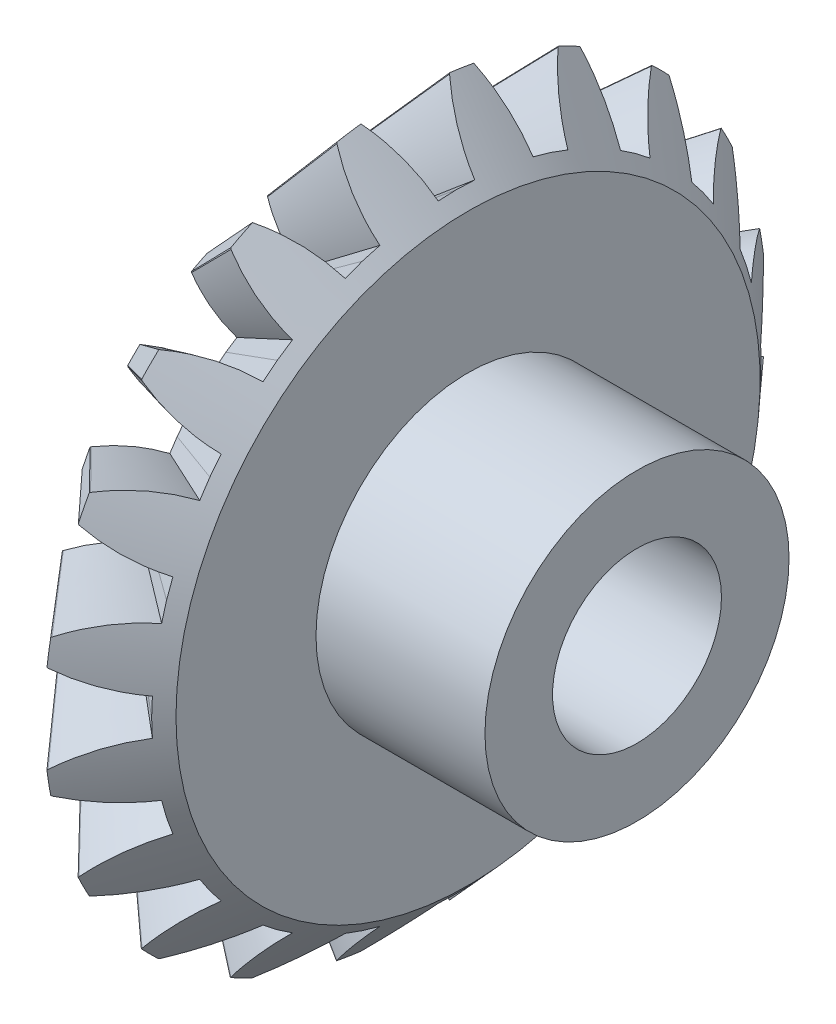
SolidWorks part; units mm, degrees
material "AISI 316 Stainless Steel Sheet (SS)"
ref_plane "Front Plane" through (0, 0, 0) normal (0, 0, 1) x (1, 0, 0)
ref_plane "Top Plane" through (0, 0, 0) normal (0, 1, 0) x (1, 0, 0)
ref_plane "Right Plane" through (0, 0, 0) normal (1, 0, 0) x (0, 0, -1)
sketch "Sketch1" plane through (0, 0, 0) normal (0, 0, 1) x (1, 0, 0)
  line L0 (0, 0) -> (123.5908, 0) construction
  line L1 (0, 0) -> (87.9001, 73.5142) construction
  line L2 (0, 0) -> (81.4883, 81.4883) construction
  line L3 (0, 0) -> (46.3388, 53.4099) construction
  line L4 (46.3388, 53.4099) -> (76.7808, 88.4972) construction
  line L5 (46.3388, 53.4099) -> (55.6393, 43.2156)
  line L7 (46.3388, 53.4099) -> (33.2321, 38.3032)
  line L8 (33.2321, 38.3032) -> (40.762, 30.7732)
  line L9 (40.762, 30.7732) -> (55.6393, 43.2156) construction
  line L10 (40.762, 30.7732) -> (42.1125, 0)
  line L12 (42.1125, 0) -> (55.6393, 0)
  line L13 (55.6393, 0) -> (55.6393, 43.2156)
  dimension "D1" = 45
  dimension "D2" = 70.71
  dimension "D3" = 5
  dimension "D5" = 20
revolve "Revolve1" add sketch "Sketch1" angle 360 about L12
ref_plane "Plane1" through (51.8824, 47.3336, 0) normal (0.7387, 0.674, 0) x (0, 0, -1)
sketch "Sketch2" plane through (51.8824, 47.3336, 0) normal (0.7387, 0.674, 0) x (0, 0, -1)
  line L0 (0, -46.7749) -> (0, 8.2251) construction
  line L4 (0, 8.2251) -> (-2.7, -3.1083) construction
  line L5 (0, -3.0249) -> (-6.5, 7.8396) construction
  line L6 (-2.7, -3.1083) -> (0, -3.0249)
  line L7 (2.7, -3.1083) -> (0, -3.0249)
  line L8 (-6.5, 7.8396) -> (-7.4216, 9.5172)
  line L9 (-7.4216, 9.5172) -> (8.7459, 9.5172)
  line L10 (8.7459, 9.5172) -> (6.5, 7.8396)
  arc A0 (0, 8.2251) -> (-6.5, 7.8396) centre (0, -46.7749) ccw construction
  circle A1 centre (0, -46.7749) radius 50 construction
  circle A2 centre (0, -46.7749) radius 43.75 construction
  arc A8 (-6.5, 7.8396) -> (-2.7, -3.1083) centre (-30.9187, -6.7695) cw
  arc A9 (6.5, 7.8396) -> (2.7, -3.1083) centre (30.9187, -6.7695) ccw
  ellipse E0 centre (0, -31.2315) end of major axis (53.4099, -31.2315) minor radius 39.4565 construction
  dimension "D1" = 110
  dimension "D2" = 100
  dimension "D3" = 87.5
  dimension "D4" = 2.7
  dimension "D5" = 6.5
sketch "Sketch4" plane through (0, 0, 0) normal (0, 0, 1) x (1, 0, 0)
  point P0 (0, 0)
loft "Cut-Loft2" cut profiles "Sketch4", "Sketch2"
pattern_circular "CirPattern1" count 20 over 360 about axis through (40.762, 0, 0) along (-1, 0, 0) of "Cut-Loft2"
sketch "Sketch5" plane through (55.6393, 0, 0) normal (1, 0, 0) x (0, 0, -1)
  circle A0 centre (0, 0) radius 12.5
  dimension "D1" = 25
extrude "Cut-Extrude1" cut sketch "Sketch5" against normal blind 63
sketch "Sketch6" plane through (55.6393, 0, 0) normal (1, 0, 0) x (0, 0, -1)
  circle A0 centre (0, 0) radius 22.5
  circle A1 centre (0, 0) radius 12.5
  dimension "D1" = 45
extrude "Boss-Extrude2" add sketch "Sketch6" along normal blind 25
